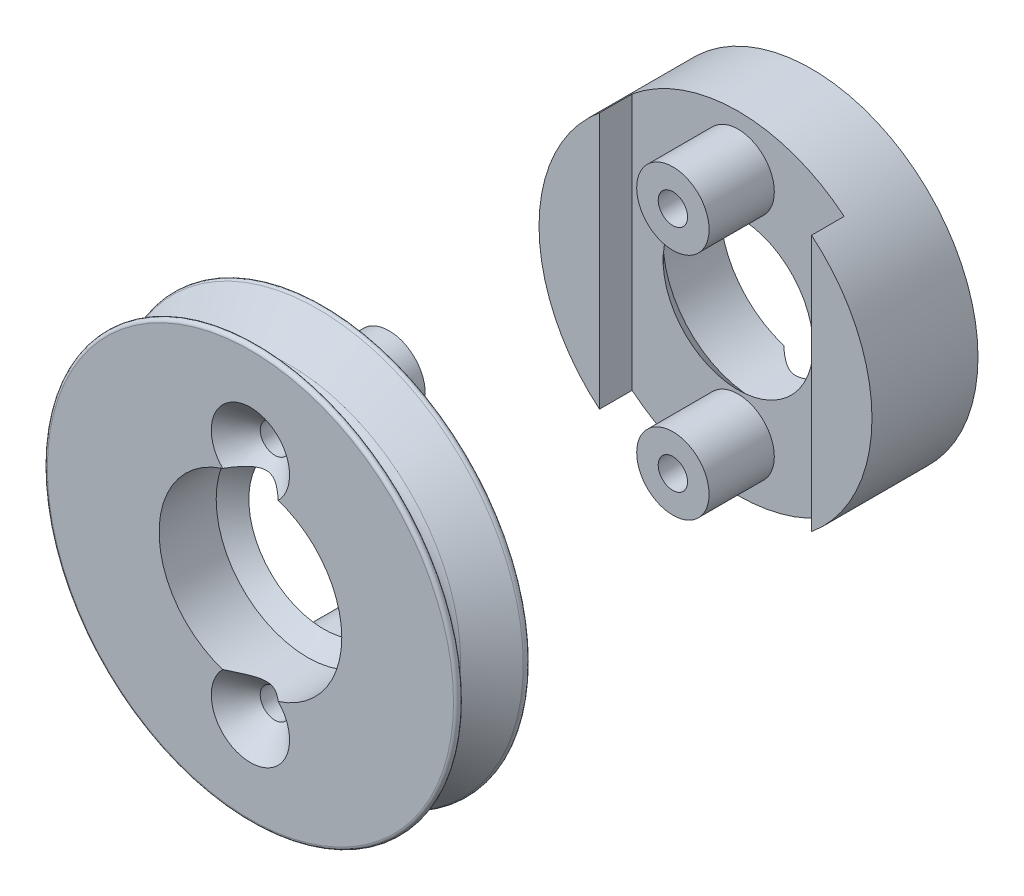
SolidWorks part; units mm, degrees
ref_plane "Front Plane" through (0, 0, 0) normal (0, 0, 1) x (1, 0, 0)
ref_plane "Top Plane" through (0, 0, 0) normal (0, 1, 0) x (1, 0, 0)
ref_plane "Right Plane" through (0, 0, 0) normal (1, 0, 0) x (0, 0, -1)
sketch "Sketch2" plane through (0, 0, 0) normal (1, 0, 0) x (0, 0, -1)
  line L0 (-2, 11.2) -> (-9, 11.2)
  line L1 (-9, 11.2) -> (-9, 24.9013)
  line L2 (-8.2241, 25.0381) -> (-6.9207, 21.457)
  line L3 (-4.2129, 20.9796) -> (-0.7064, 25.1584)
  line L4 (0, 24.9013) -> (0, 9.2)
  line L6 (-2, 11.2) -> (0, 9.2)
  line L7 (0, 0) -> (7.0902, 0) construction
  arc A0 (-9, 24.9013) -> (-8.2241, 25.0381) centre (-8.6, 24.9013) cw
  arc A1 (-6.9207, 21.457) -> (-4.2129, 20.9796) centre (-5.429, 22) ccw
  arc A2 (-0.7064, 25.1584) -> (0, 24.9013) centre (-0.4, 24.9013) cw
  point P11 (-2, 10.7146)
  point P12 (-1.5934, 11.2)
  point P14 (-1.9256, 11.2)
  point P15 (0, 9.3147)
  dimension "D1" = 11.2
  dimension "D4" = 1.5875
  dimension "D7" = 0.4
  dimension "D2" = 7
  dimension "D3" = 40
  dimension "D5" = 2
  dimension "D6" = 45
  dimension "D8" = 20
  dimension "D9" = 22
revolve "Revolve1" add sketch "Sketch2" angle 360 about L7
sketch "Sketch3" plane through (0, 0, 0) normal (0, 0, -1) x (-1, 0, 0)
  line L0 (0, 9.625) -> (0, -9.625) construction
  circle A0 centre (0, 14.0625) radius 4.4375
  circle A1 centre (0, -14.0625) radius 4.4375
  point P4 (0, 18.5)
  point P5 (0, -18.5)
  point P7 (0, -9.625)
  point P11 (0, 0)
  point P12 (0, 0)
  dimension "D1" = 19.25
  dimension "D2" = 37
extrude "Boss-Extrude1" add sketch "Sketch3" along normal blind 8
sketch "Sketch4" plane through (0, 0, -8) normal (0, 0, -1) x (-1, 0, 0)
  circle A0 centre (0, 14.0625) radius 1.8
  circle A1 centre (0, -14.0625) radius 1.8
  dimension "D1" = 3.6
extrude "Cut-Extrude1" cut sketch "Sketch4" against normal through all
chamfer "Chamfer1" distance 3 angle 45 2 edges at (-1.8, -14.0625, 9) (-1.8, 14.0625, 9)
ref_plane "Plane1" through (0, 0, -25.4) normal (0, 0, -1) x (-1, 0, 0)
mirror "Mirror2" about plane through (0, 0, -25.4) normal (0, 0, -1) of bodies 103
sketch "Sketch8" plane through (0, 0, -59.8) normal (0, 0, -1) x (-1, 0, 0)
  circle A0 centre (0, 0) radius 20.4125
  circle A1 centre (0, 0) radius 20.4125 construction
  circle A2 centre (0, 0) radius 31.2181
extrude "Cut-Extrude3" cut sketch "Sketch8" against normal blind 25
sketch "Sketch9" plane through (0, 0, -50.8) normal (0, 0, 1) x (1, 0, 0)
  line L1 (13, -35.7575) -> (-13, -35.7575)
  line L2 (13, -35.7575) -> (13, 35.7575)
  line L3 (13, 35.7575) -> (-13, 35.7575)
  line L4 (-13, -35.7575) -> (-13, 35.7575)
  line L5 (13, -35.7575) -> (-13, 35.7575) construction
  line L6 (13, 35.7575) -> (-13, -35.7575) construction
  line L7 (26.8446, -43.6097) -> (-26.8446, -43.6097)
  line L8 (26.8446, -43.6097) -> (26.8446, 43.6097)
  line L9 (26.8446, 43.6097) -> (-26.8446, 43.6097)
  line L10 (-26.8446, -43.6097) -> (-26.8446, 43.6097)
  line L11 (26.8446, -43.6097) -> (-26.8446, 43.6097) construction
  line L12 (26.8446, 43.6097) -> (-26.8446, -43.6097) construction
  point P0 (0, 0)
  point P5 (0, 0)
  circle M6 centre (0, 0) radius 20.4125
  dimension "D1" = 26
extrude "Boss-Extrude4" add sketch "Sketch9" along normal blind 4 contours L4 M6 | L2 M6 region at (16.0166, 0, -50.8) region at (-16.0166, 0, -50.8)
